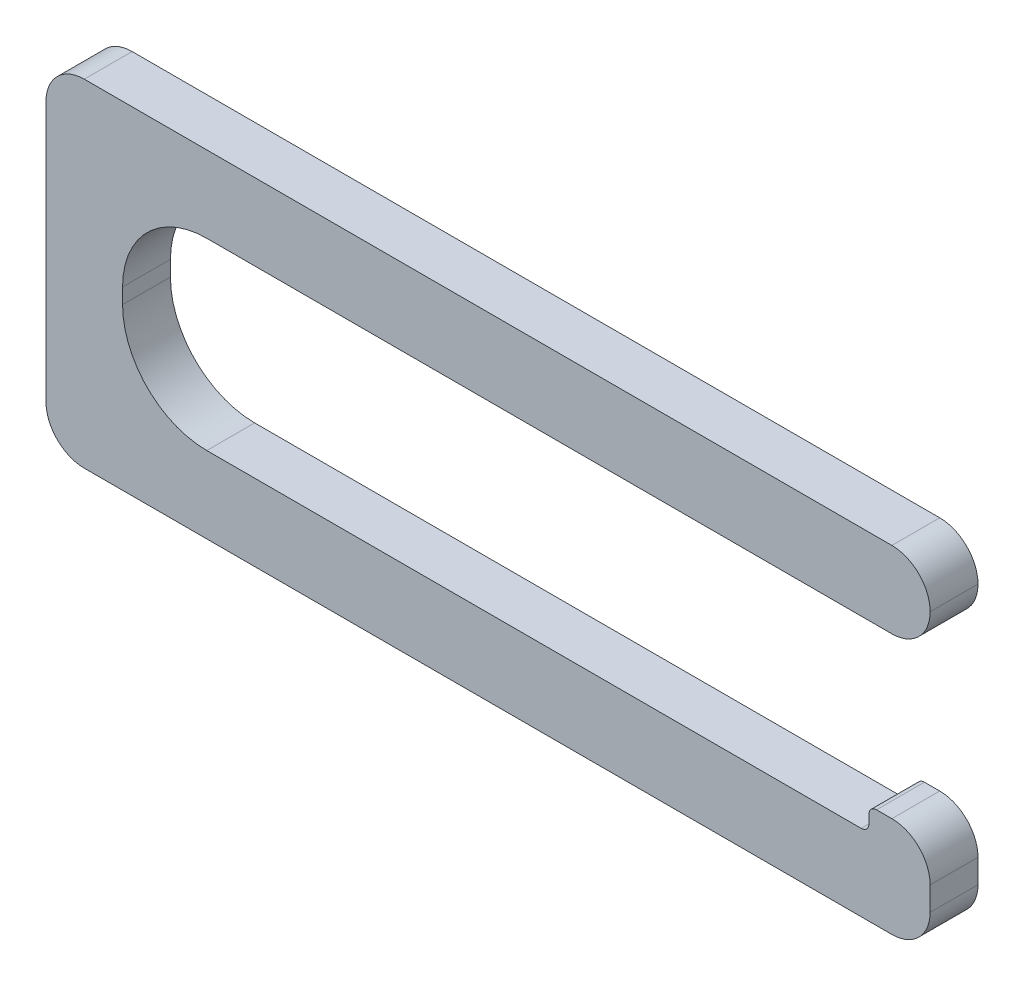
SolidWorks part; units mm, degrees
ref_plane "Front Plane" through (0, 0, 0) normal (0, 0, 1) x (1, 0, 0)
ref_plane "Top Plane" through (0, 0, 0) normal (0, 1, 0) x (1, 0, 0)
ref_plane "Right Plane" through (0, 0, 0) normal (1, 0, 0) x (0, 0, -1)
sketch "Sketch1" plane through (0, 0, 0) normal (0, 0, 1) x (1, 0, 0)
  line L0 (5.6519, 12.5186) -> (34.9792, 12.5186)
  line L1 (34.9792, 12.5186) -> (34.9792, 15.846)
  line L2 (32.9472, 15.0586) -> (8.1919, 15.0586)
  line L3 (8.1919, 15.0586) -> (8.1919, 21.1546)
  line L4 (8.1919, 21.1546) -> (34.9792, 21.1546)
  line L5 (34.9792, 21.1546) -> (34.9792, 23.6946)
  line L6 (34.9792, 23.6946) -> (5.6519, 23.6946)
  line L7 (5.6519, 23.6946) -> (5.6519, 12.5186)
  line L8 (16.7928, 15.0586) -> (32.9472, 15.0586) construction
  line L9 (34.9792, 15.846) -> (34.9792, 17.624) construction
  line L10 (32.9472, 15.0586) -> (32.9472, 15.846)
  line L11 (32.9472, 15.846) -> (34.9792, 15.846)
  line L13 (32.9472, 15.0586) -> (32.9472, 15.846) construction
  line L14 (16.7674, 15.846) -> (34.9792, 15.846) construction
  dimension "D1" = 2.54
  dimension "D2" = 2.54
  dimension "D3" = 2.54
  dimension "D4" = 6.096
extrude "Boss-Extrude1" add sketch "Sketch1" along normal blind 1.5875
fillet "Fillet1" radius 1.27 6 edges at (5.6519, 12.5186, 0.7937) (34.9792, 12.5186, 0.7937) (34.9792, 15.846, 0.7937) (5.6519, 23.6946, 0.7937) (34.9792, 21.1546, 0.7937) (34.9792, 23.6946, 0.7937)
fillet "Fillet2" radius 0.254 2 edges at (32.9472, 15.0586, 0.7937) (32.9472, 15.846, 0.7937)
fillet "Fillet3" radius 2.794 2 edges at (8.1919, 15.0586, 0.7937) (8.1919, 21.1546, 0.7937)
